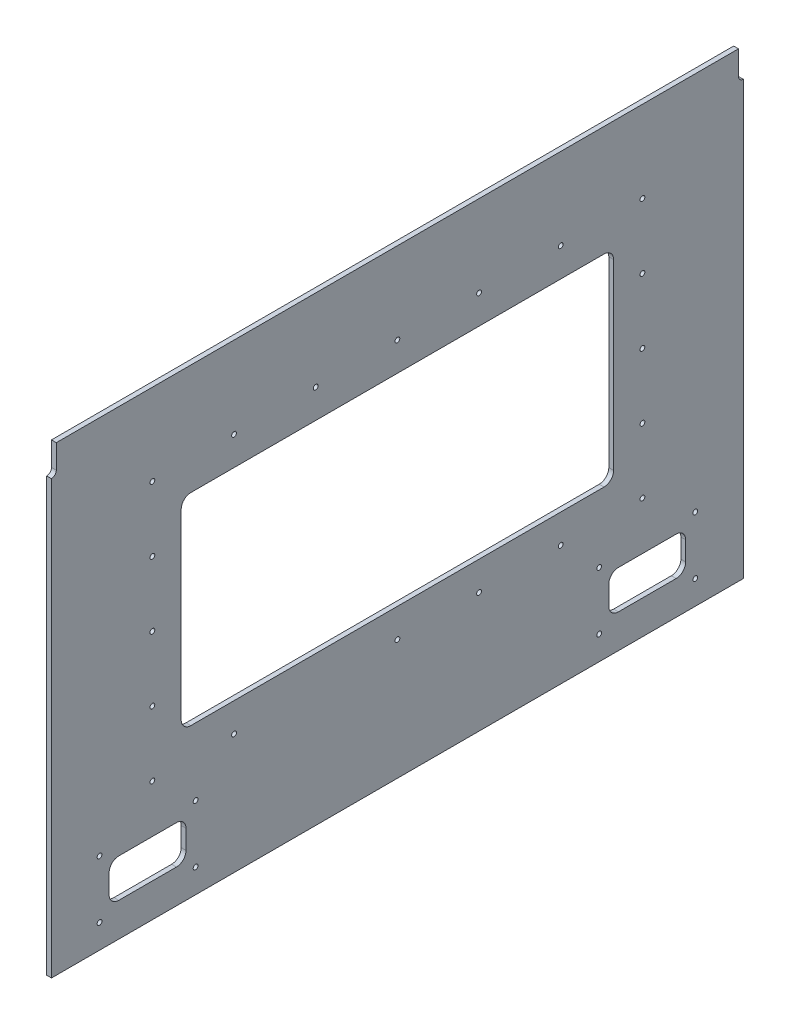
SolidWorks part; units mm, degrees
material "6061 Alloy"
ref_plane "Front Plane" through (0, 0, 0) normal (0, 0, 1) x (1, 0, 0)
ref_plane "Top Plane" through (0, 0, 0) normal (0, 1, 0) x (1, 0, 0)
ref_plane "Right Plane" through (0, 0, 0) normal (1, 0, 0) x (0, 0, -1)
sketch "Sketch1" plane through (-304.8, 0, 0) normal (-1, 0, 0) x (0, 0, 1)
  line L1 (-457.2, 0) -> (457.2, 0)
  line L2 (-457.2, 0) -> (-457.2, 609.6)
  line L3 (-457.2, 609.6) -> (457.2, 609.6)
  line L4 (457.2, 0) -> (457.2, 609.6)
  dimension "D1" = 609.6
extrude "Boss-Extrude1" add sketch "Sketch1" along normal blind 6.35 separate body
sketch "Sketch2" plane through (-311.15, 0, 0) normal (-1, 0, 0) x (0, 0, 1)
  line L0 (457.2, 609.6) -> (-457.2, 609.6) construction
  line L1 (-285.75, 463.55) -> (285.75, 463.55)
  line L2 (-285.75, 463.55) -> (-285.75, 196.85)
  line L3 (-285.75, 196.85) -> (285.75, 196.85)
  line L4 (285.75, 463.55) -> (285.75, 196.85)
  line L6 (-457.2, 609.6) -> (-457.2, 0) construction
  point P6 (0, 609.6)
  point P7 (0, 463.55)
  point P11 (-457.2, 304.8)
  dimension "D1" = 571.5
  dimension "D2" = 266.7
  dimension "D3" = 107.95
extrude "Cut-Extrude1" cut sketch "Sketch2" against normal through all
sketch "Sketch3" plane through (-311.15, 0, 0) normal (-1, 0, 0) x (0, 0, 1)
  line L0 (-457.2, 609.6) -> (-457.2, 0) construction
  line L1 (-381, 95.25) -> (-279.4, 95.25)
  line L2 (-381, 95.25) -> (-381, 44.45)
  line L3 (-381, 44.45) -> (-279.4, 44.45)
  line L4 (-279.4, 95.25) -> (-279.4, 44.45)
  line L6 (-279.4, 95.25) -> (-279.4, 139.7) construction
  line L7 (-327.66, 139.7) -> (327.66, 139.7) construction
  line L8 (-279.4, 44.45) -> (-279.4, 6.35) construction
  line L10 (-457.2, 0) -> (457.2, 0) construction
  line L11 (-393.7, 107.95) -> (-266.7, 107.95) construction
  line L12 (-393.7, 107.95) -> (-393.7, 31.75) construction
  line L13 (0, 0) -> (0, 264.8995) construction
  line L14 (279.4, 95.25) -> (279.4, 44.45)
  line L15 (381, 44.45) -> (279.4, 44.45)
  line L16 (381, 95.25) -> (279.4, 95.25)
  line L17 (381, 95.25) -> (381, 44.45)
  circle A0 centre (-393.7, 107.95) radius 12.7 construction
  circle A1 centre (-266.7, 107.95) radius 12.7 construction
  circle A2 centre (-266.7, 31.75) radius 12.7 construction
  circle A3 centre (-393.7, 31.75) radius 12.7 construction
  point P20 (-330.2, 107.95)
  point P21 (-330.2, 95.25)
  point P22 (-393.7, 69.85)
  point P23 (-381, 69.85)
  dimension "D7" = 25.4
  dimension "D2" = 101.6
  dimension "D3" = 76.2
  dimension "D4" = 6.35
  dimension "D5" = 38.1
  dimension "D6" = 44.45
  dimension "D8" = 12.7
  dimension "D9" = 12.7
extrude "Cut-Extrude2" cut sketch "Sketch3" against normal through all
fillet "Fillet1" radius 12.7 12 edges at (-307.975, 463.55, -285.75) (-307.975, 463.55, 285.75) (-307.975, 196.85, -285.75) (-307.975, 196.85, 285.75) (-307.975, 44.45, -279.4) (-307.975, 95.25, -279.4) (-307.975, 95.25, -381) (-307.975, 44.45, -381) (-307.975, 44.45, 381) (-307.975, 95.25, 381) (-307.975, 95.25, 279.4) (-307.975, 44.45, 279.4)
sketch "Sketch4" plane through (-311.15, 0, 0) normal (-1, 0, 0) x (0, 0, 1)
  circle A0 centre (-107.95, 158.75) radius 3.175 construction
  circle A1 centre (0, 158.75) radius 3.175 construction
  circle A2 centre (215.9, 158.75) radius 3.175 construction
  circle A3 centre (323.85, 158.75) radius 3.175 construction
  circle A13 centre (323.85, 244.475) radius 3.175 construction
  circle A14 centre (-323.85, 244.475) radius 3.175 construction
  circle A16 centre (323.85, 244.475) radius 3.175
  circle A17 centre (-323.85, 244.475) radius 3.175
  circle A22 centre (-107.95, 158.75) radius 3.175
  circle A23 centre (0, 158.75) radius 3.175
  circle A24 centre (215.9, 158.75) radius 3.175
  circle A25 centre (323.85, 158.75) radius 3.175
  circle A39 centre (-323.85, 158.75) radius 3.175 construction
  circle A40 centre (-215.9, 158.75) radius 3.175 construction
  circle A44 centre (-323.85, 158.75) radius 3.175
  circle A45 centre (-215.9, 158.75) radius 3.175
  circle A46 centre (266.7, 31.75) radius 3.175 construction
  circle A47 centre (393.7, 31.75) radius 3.175 construction
  circle A48 centre (266.7, 107.95) radius 3.175 construction
  circle A49 centre (393.7, 107.95) radius 3.175 construction
  circle A50 centre (-266.7, 31.75) radius 3.175 construction
  circle A51 centre (-393.7, 31.75) radius 3.175 construction
  circle A52 centre (-393.7, 107.95) radius 3.175 construction
  circle A53 centre (-266.7, 107.95) radius 3.175 construction
  circle A54 centre (266.7, 31.75) radius 3.175
  circle A55 centre (393.7, 31.75) radius 3.175
  circle A56 centre (266.7, 107.95) radius 3.175
  circle A57 centre (393.7, 107.95) radius 3.175
  circle A58 centre (-266.7, 31.75) radius 3.175
  circle A59 centre (-393.7, 31.75) radius 3.175
  circle A60 centre (-393.7, 107.95) radius 3.175
  circle A61 centre (-266.7, 107.95) radius 3.175
  circle A62 centre (323.85, 330.2) radius 3.175 construction
  circle A63 centre (323.85, 415.925) radius 3.175 construction
  circle A64 centre (323.85, 501.65) radius 3.175 construction
  circle A65 centre (215.9, 501.65) radius 3.175 construction
  circle A66 centre (107.95, 501.65) radius 3.175 construction
  circle A67 centre (0, 501.65) radius 3.175 construction
  circle A68 centre (-107.95, 501.65) radius 3.175 construction
  circle A69 centre (-215.9, 501.65) radius 3.175 construction
  circle A70 centre (-323.85, 501.65) radius 3.175 construction
  circle A71 centre (-323.85, 415.925) radius 3.175 construction
  circle A72 centre (-323.85, 330.2) radius 3.175 construction
  circle A73 centre (323.85, 330.2) radius 3.175
  circle A74 centre (323.85, 415.925) radius 3.175
  circle A75 centre (323.85, 501.65) radius 3.175
  circle A76 centre (215.9, 501.65) radius 3.175
  circle A77 centre (107.95, 501.65) radius 3.175
  circle A78 centre (0, 501.65) radius 3.175
  circle A79 centre (-107.95, 501.65) radius 3.175
  circle A80 centre (-215.9, 501.65) radius 3.175
  circle A81 centre (-323.85, 501.65) radius 3.175
  circle A82 centre (-323.85, 415.925) radius 3.175
  circle A83 centre (-323.85, 330.2) radius 3.175
extrude "Cut-Extrude3" cut sketch "Sketch4" against normal through all
sketch "Sketch5" plane through (-311.15, 0, 0) normal (-1, 0, 0) x (0, 0, 1)
  line L1 (-457.2, 584.2) -> (-457.2, 577.596) construction
  line L2 (-457.2, 577.596) -> (-450.85, 577.596) construction
  line L3 (-450.85, 577.596) -> (-450.85, 584.2) construction
  line L12 (-457.2, 603.25) -> (-457.2, 584.2) construction
  line L13 (-450.85, 603.25) -> (-450.85, 584.2) construction
  line L14 (-457.2, 603.25) -> (-450.85, 603.25) construction
  line L15 (-457.2, 584.2) -> (-457.2, 577.596) construction
  line L16 (-457.2, 577.596) -> (-450.85, 577.596) construction
  line L17 (-450.85, 577.596) -> (-450.85, 584.2) construction
  line L18 (-457.2, 603.25) -> (-457.2, 584.2) construction
  line L19 (-450.85, 603.25) -> (-450.85, 584.2) construction
  line L20 (-457.2, 603.25) -> (-450.85, 603.25) construction
  line L21 (-450.85, 609.6) -> (-450.85, 571.5)
  line L22 (-450.85, 571.5) -> (-457.2, 571.5)
  line L23 (457.2, 609.6) -> (-457.2, 609.6) construction
  line L24 (457.2, 609.6) -> (-457.2, 609.6)
  line L25 (-457.2, 609.6) -> (-457.2, 0) construction
  line L26 (-457.2, 609.6) -> (-457.2, 0)
  line L27 (457.2, 0) -> (457.2, 609.6) construction
  line L28 (457.2, 0) -> (457.2, 609.6)
  line L29 (450.85, 609.6) -> (450.85, 571.5)
  line L30 (450.85, 571.5) -> (457.2, 571.5)
  dimension "D1" = 6.35
  dimension "D2" = 38.1
extrude "Cut-Extrude4" cut sketch "Sketch5" against normal through all contours L24 L26 L22 L21 | L29 L30 L28 L24 region at (-311.15, 590.55, 454.025) region at (-311.15, 590.55, -454.025)
fillet "Fillet2" radius 6.604 2 edges at (-307.975, 571.5, 450.85) (-307.975, 571.5, -450.85)
equation "\"D3@Sketch2\"=(\"D2@Sketch2\"/2)-1"
equation "\"D9@Sketch3\"=\"D8@Sketch3\""
